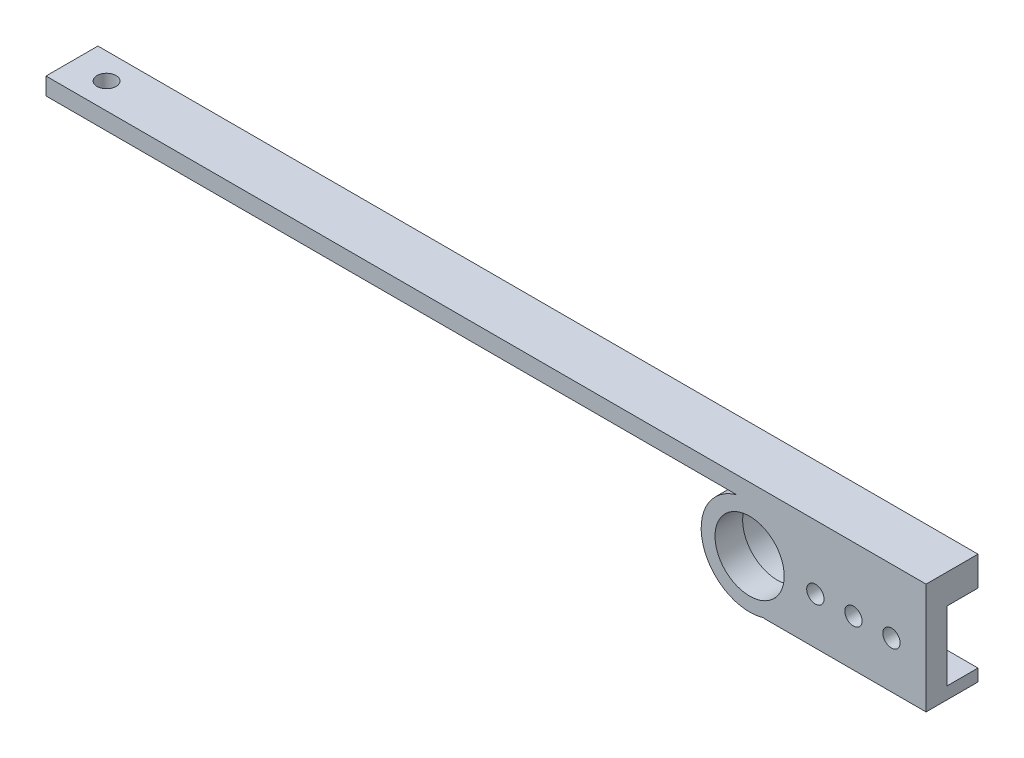
SolidWorks part; units mm, degrees
ref_plane "前视基准面" through (0, 0, 0) normal (0, 0, 1) x (1, 0, 0)
ref_plane "上视基准面" through (0, 0, 0) normal (0, 1, 0) x (1, 0, 0)
ref_plane "右视基准面" through (0, 0, 0) normal (1, 0, 0) x (0, 0, -1)
sketch "草图1" plane through (0, 0, 0) normal (0, 0, 1) x (1, 0, 0)
  line L1 (20, -10) -> (-20, -10)
  line L2 (20, -10) -> (20, 10)
  line L3 (20, 10) -> (-20, 10)
  line L4 (-20, -10) -> (-20, 10)
  line L5 (20, -10) -> (-20, 10) construction
  line L6 (20, 10) -> (-20, -10) construction
  point P0 (0, 0)
  dimension "D1" = 40
  dimension "D2" = 20
extrude "凸台-拉伸1" add sketch "草图1" along normal blind 6
sketch "草图2" plane through (0, 0, 6) normal (0, 0, 1) x (1, 0, 0)
  line L0 (20, -10) -> (20, 10) construction
  circle A0 centre (10, 0) radius 2.5
  circle A1 centre (-1, 0) radius 2.5
  circle A2 centre (-12, 0) radius 2.5
  dimension "D1" = 10
  dimension "D2" = 5
  dimension "D3" = 3
extrude "切除-拉伸1" cut sketch "草图2" against normal through all
sketch "草图3" plane through (0, 0, 6) normal (0, 0, 1) x (1, 0, 0)
  line L0 (20, 13.5) -> (20, 10)
  line L1 (20, -13.5) -> (-26.894, -13.5)
  line L3 (20, 13.5) -> (-26.894, 13.5)
  line L4 (-20, 10) -> (-20, -10)
  line L5 (-20, -10) -> (20, -10)
  line L6 (20, -10) -> (20, 10)
  line L7 (20, 10) -> (-20, 10)
  line L8 (-20, 10) -> (-20, -10)
  line L9 (-20, -10) -> (20, -10)
  line L10 (20, -10) -> (20, 10)
  line L11 (20, 10) -> (-20, 10)
  line L12 (-26.894, -13.5) -> (-26.894, 13.5)
  line L13 (20, -10.0394) -> (-26.894, 13.5) construction
  line L14 (20, 10.0394) -> (-26.894, -13.5) construction
  line L15 (20, -10) -> (20, -13.5)
  circle A0 centre (-31, 0) radius 11
  circle A1 centre (-31, 0) radius 14
  point P2 (0, 0)
  line M10 (-20, 10) -> (-20, -10)
  line M11 (-20, -10) -> (20, -10)
  line M13 (20, 10) -> (-20, 10)
  dimension "D3" = 22
  dimension "D4" = 28
  dimension "D2" = 3.5
  dimension "D1" = 0
extrude "凸台-拉伸2" add sketch "草图3" against normal blind 15 contours L3 A1 L1 L12 A0 | A1 L1 L15 M11 M10 | L1 A1 L8 A0 L12 | L8 A1 L3 L12 A0 | L8 A1 | A1 L0 L3 M10 M13 region at (-1.9449, 11.7771, 6) region at (-1.9449, -11.7771, 6) region at (-23.0173, 9.0328, 6) region at (-27.2274, 11.7946, 6) region at (-18.7882, 0, 6) region at (-23.0173, -9.0328, 6)
sketch "草图5" plane through (0, 0, 6) normal (0, 0, 1) x (1, 0, 0)
  circle A0 centre (-31, 0) radius 10
  circle A1 centre (-31, 0) radius 11 construction
  circle A2 centre (-31, 0) radius 11
  dimension "D1" = 20
extrude "凸台-拉伸3" add sketch "草图5" against normal blind 8
sketch "草图6" plane through (0, 0, 6) normal (0, 0, 1) x (1, 0, 0)
  circle A0 centre (-31, 0) radius 8.5
  circle A1 centre (-31, 0) radius 10 construction
  circle A2 centre (-31, 0) radius 10
  dimension "D1" = 17
sketch "草图7" plane through (0, 13.5, 0) normal (0, 1, 0) x (1, 0, 0)
  circle A0 centre (-17.1666, 1.953) radius 2.6594
sketch "草图8" plane through (20, 0, 0) normal (1, 0, 0) x (0, 0, -1)
  line L1 (-6, 13.5) -> (9, 13.5)
  line L2 (-6, 13.5) -> (-6, 18.5)
  line L3 (-6, 18.5) -> (9, 18.5)
  line L4 (9, 13.5) -> (9, 18.5)
  dimension "D1" = 5
extrude "凸台-拉伸4" add sketch "草图8" against normal blind 500
sketch "草图9" plane through (0, 0, -9) normal (0, 0, -1) x (-1, 0, 0)
  line L1 (24.4567, 15.8334) -> (28.494, 15.8334)
  line L2 (24.4567, 15.8334) -> (24.4567, 12.469)
  line L3 (24.4567, 12.469) -> (28.494, 12.469)
  line L4 (28.494, 15.8334) -> (28.494, 12.469)
extrude "凸台-拉伸5" add sketch "草图9" against normal through all
sketch "草图10" plane through (0, 18.5, 0) normal (0, 1, 0) x (1, 0, 0)
  line L0 (-234.3163, -8.9161) -> (-234.3163, 9)
  line L1 (-234.3163, -8.9161) -> (-95.8824, -8.9161) construction
  line L2 (-234.3163, 238.5858) -> (-234.3163, -131.4142) construction
  line L3 (-480, 9) -> (20, 9) construction
sketch "草图11" plane through (0, 18.5, 0) normal (0, 1, 0) x (1, 0, 0)
  line L1 (-234.3163, -8.9161) -> (-495.6366, -8.9161)
  line L2 (-234.3163, -8.9161) -> (-234.3163, 25.3653)
  line L3 (-234.3163, 25.3653) -> (-495.6366, 25.3653)
  line L4 (-495.6366, -8.9161) -> (-495.6366, 25.3653)
extrude "切除-拉伸2" cut sketch "草图11" against normal through all
sketch "草图12" plane through (0, 18.5, 0) normal (0, 1, 0) x (1, 0, 0)
  line L0 (-224.3163, 9) -> (-224.3163, -6)
  line L1 (-234.3163, 9) -> (20, 9) construction
  line L2 (-234.3163, -6) -> (20, -6) construction
  line L3 (-234.3163, -8.9161) -> (-234.3163, 9) construction
  circle A0 centre (-224.3163, 1.5) radius 2.75
  dimension "D2" = 5.5
  dimension "D1" = 10
extrude "切除-拉伸3" cut sketch "草图12" against normal blind 10 contours L0 A0 | A0 region at (-223.1491, 18.5, -1.5)
